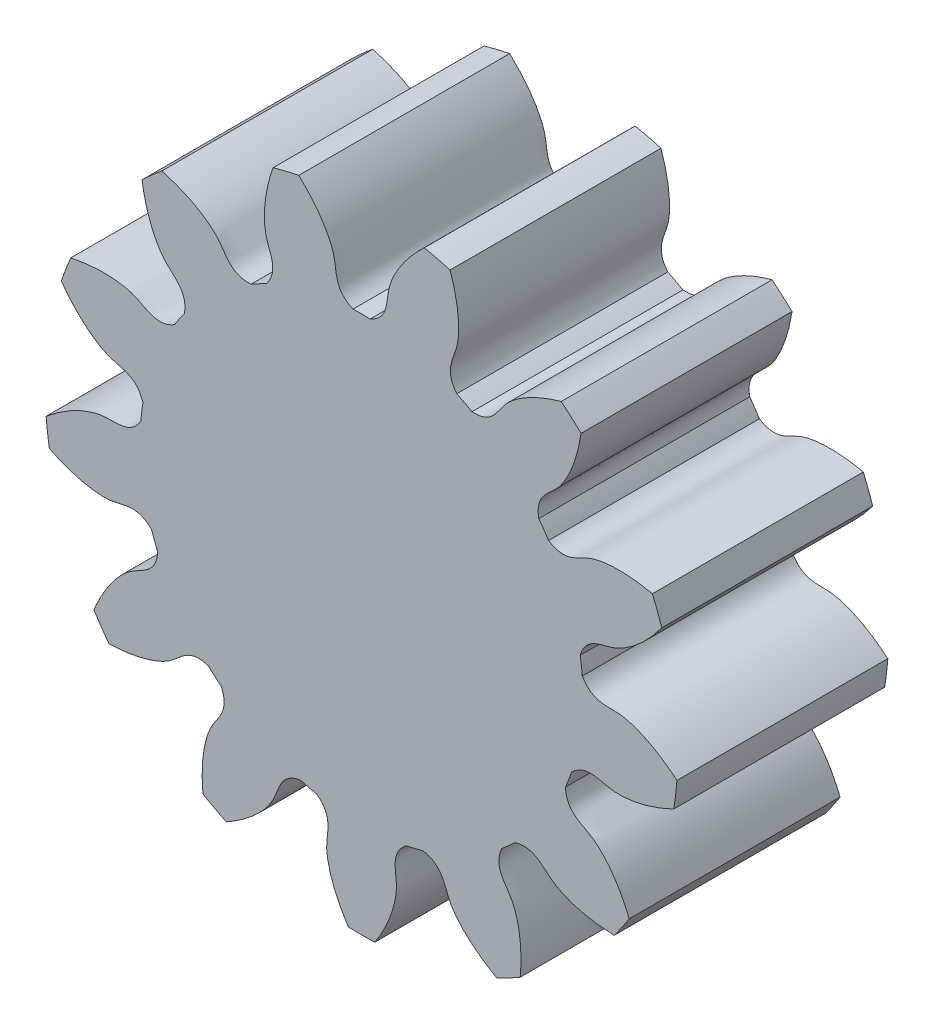
SolidWorks part; units mm, degrees
ref_plane "前视基准面" through (0, 0, 0) normal (0, 0, 1) x (1, 0, 0)
ref_plane "上视基准面" through (0, 0, 0) normal (0, 1, 0) x (1, 0, 0)
ref_plane "右视基准面" through (0, 0, 0) normal (1, 0, 0) x (0, 0, -1)
sketch "草图1" plane through (0, 0, 0) normal (0, 0, 1) x (1, 0, 0)
  circle A0 centre (0, 0) radius 7.5
extrude "凸台-拉伸1" add sketch "草图1" along normal blind 5
ref_axis "基准轴1" through (0, 0, -0.25) along (0, 0, 1)
sketch "草图2" plane through (0, 0, 0) normal (0, 0, 1) x (1, 0, 0)
  line L0 (0, 0) -> (0, 7.5) construction
  circle A0 centre (0, 0) radius 7.5 construction
  arc A1 (0.2033, 5.2461) -> (-0.2033, 5.2461) centre (0, 0) ccw
  arc A2 (3.3109, 8.455) -> (-3.3109, 8.455) centre (0, 0) ccw
  spline S0 degree 3 poles (0.2033, 5.2461) (0.6627, 5.4496) (0.5734, 5.8312) (0.6699, 6.1707) (0.6767, 6.1929) (0.6847, 6.2173) (0.694, 6.2438) (0.7046, 6.2724) (0.7168, 6.3031) (0.7304, 6.3358) (0.7458, 6.3704) (0.7628, 6.407) (0.7817, 6.4453) (0.8024, 6.4855) (0.8251, 6.5274) (0.8498, 6.571) (0.8767, 6.6161) (0.9057, 6.6628) (0.937, 6.7109) (0.9706, 6.7605) (1.0066, 6.8113) (1.0451, 6.8634) (1.0861, 6.9166) (1.1297, 6.9709) (1.176, 7.0262) (1.2249, 7.0824) (1.2766, 7.1394) (1.3311, 7.1972) (1.3884, 7.2556) (1.4487, 7.3145) (1.5119, 7.3739) (1.5781, 7.4337) (1.6473, 7.4937) (1.7196, 7.5539) (1.795, 7.6142) (1.8735, 7.6744) (1.9551, 7.7345) (2.04, 7.7944) (2.128, 7.8539) (2.2193, 7.913) (2.3138, 7.9715) (2.4116, 8.0294) (2.5126, 8.0865) (2.6169, 8.1428) (2.7245, 8.198) (2.8354, 8.2522) (2.9495, 8.3051) (3.1076, 8.3747) (3.2288, 8.4237) (3.3109, 8.455) knots 0 0 0 0 0.219123 0.223606 0.228617 0.234155 0.240221 0.246814 0.253934 0.261582 0.269758 0.27846 0.287691 0.297448 0.307733 0.318546 0.329886 0.341753 0.354148 0.36707 0.38052 0.394497 0.409002 0.424034 0.439594 0.455681 0.472295 0.489437 0.507106 0.525303 0.544027 0.563279 0.583058 0.603364 0.624198 0.645559 0.667448 0.689865 0.712808 0.736279 0.760278 0.784804 0.809857 0.835438 0.861547 0.888182 0.915346 0.943036 1 1 1 1
  spline S1 degree 3 poles (-0.2033, 5.2461) (-0.6627, 5.4496) (-0.5734, 5.8312) (-0.6699, 6.1707) (-0.6767, 6.1929) (-0.6847, 6.2173) (-0.694, 6.2438) (-0.7046, 6.2724) (-0.7168, 6.3031) (-0.7304, 6.3358) (-0.7458, 6.3704) (-0.7628, 6.407) (-0.7817, 6.4453) (-0.8024, 6.4855) (-0.8251, 6.5274) (-0.8498, 6.571) (-0.8767, 6.6161) (-0.9057, 6.6628) (-0.937, 6.7109) (-0.9706, 6.7605) (-1.0066, 6.8113) (-1.0451, 6.8634) (-1.0861, 6.9166) (-1.1297, 6.9709) (-1.176, 7.0262) (-1.2249, 7.0824) (-1.2766, 7.1394) (-1.3311, 7.1972) (-1.3884, 7.2556) (-1.4487, 7.3145) (-1.5119, 7.3739) (-1.5781, 7.4337) (-1.6473, 7.4937) (-1.7196, 7.5539) (-1.795, 7.6142) (-1.8735, 7.6744) (-1.9551, 7.7345) (-2.04, 7.7944) (-2.128, 7.8539) (-2.2193, 7.913) (-2.3138, 7.9715) (-2.4116, 8.0294) (-2.5126, 8.0865) (-2.6169, 8.1428) (-2.7245, 8.198) (-2.8354, 8.2522) (-2.9495, 8.3051) (-3.1076, 8.3747) (-3.2288, 8.4237) (-3.3109, 8.455) knots 0 0 0 0 0.219123 0.223606 0.228617 0.234155 0.240221 0.246814 0.253934 0.261582 0.269758 0.27846 0.287691 0.297448 0.307733 0.318546 0.329886 0.341753 0.354148 0.36707 0.38052 0.394497 0.409002 0.424034 0.439594 0.455681 0.472295 0.489437 0.507106 0.525303 0.544027 0.563279 0.583058 0.603364 0.624198 0.645559 0.667448 0.689865 0.712808 0.736279 0.760278 0.784804 0.809857 0.835438 0.861547 0.888182 0.915346 0.943036 1 1 1 1
extrude "切除-拉伸1" cut sketch "草图2" along normal through all
pattern_circular "阵列(圆周)1" count 13 every 27.692 about axis through (0, 0, -0.25) along (0, 0, 1) of "切除-拉伸1"
sketch "草图3" plane through (0, 0, 0) normal (0, 0, 1) x (1, 0, 0)
  circle A0 centre (0, 0) radius 6.5 construction
  dimension "Dn" = 13
